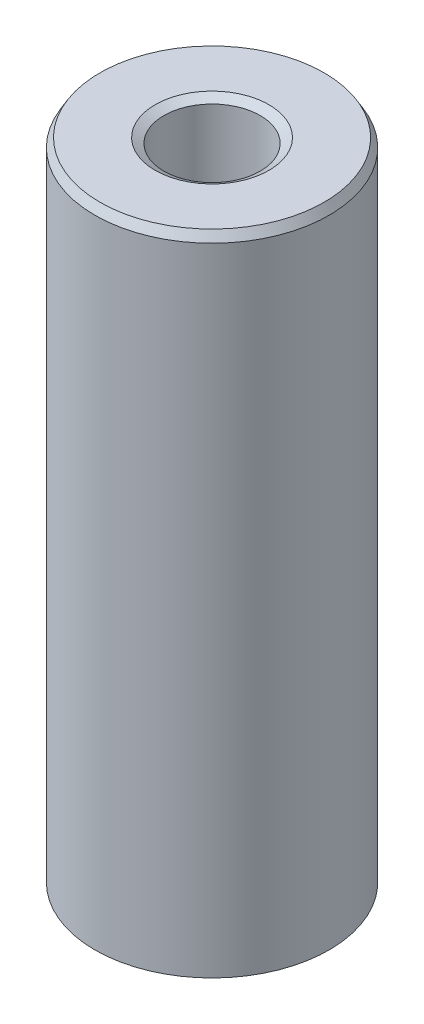
SolidWorks part; units mm, degrees
ref_plane "Front Plane" through (0, 0, 0) normal (0, 0, 1) x (1, 0, 0)
ref_plane "Top Plane" through (0, 0, 0) normal (0, 1, 0) x (1, 0, 0)
ref_plane "Right Plane" through (0, 0, 0) normal (1, 0, 0) x (0, 0, -1)
sketch "Sketch1" plane through (0, 0, 0) normal (0, 1, 0) x (1, 0, 0)
  circle A0 centre (0, 0) radius 52.5
  dimension "SLEEVE_OD" = 105
extrude "Boss-Extrude1" add sketch "Sketch1" along normal blind 291.2798
sketch "Sketch2" plane through (0, 0, 0) normal (0, 1, 0) x (1, 0, 0)
  circle A0 centre (0, 0) radius 21.5887
  dimension "BORE_D" = 43.1773
extrude "Cut-Extrude1" cut sketch "Sketch2" along normal through all
chamfer "Chamfer1" distance 3.9088 angle 30 4 edges at (0, 291.2798, 21.5887) (0, 0, 21.5887) (0, 0, 52.5) (0, 291.2798, 52.5) first distance on face at (0, 291.2798, 21.5887) first distance on face at (0, 0, 21.5887) first distance on face at (0, 291.2798, 52.5)
